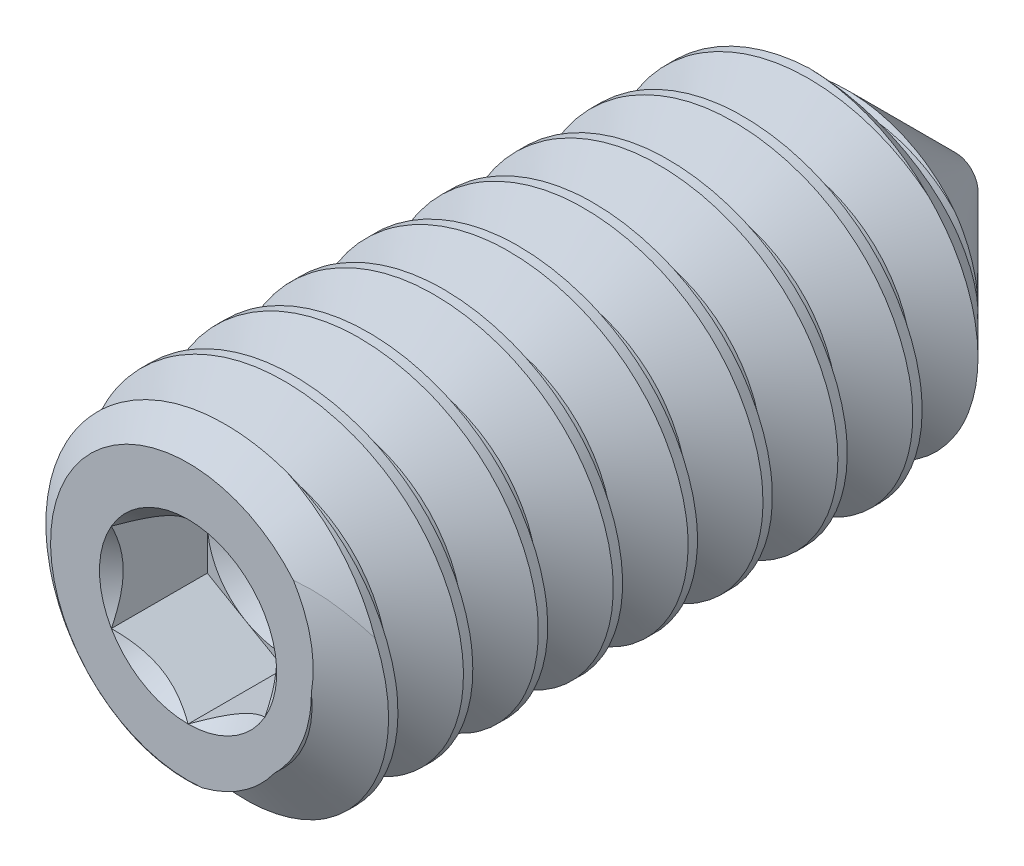
SolidWorks part; units mm, degrees
ref_plane "Front" through (0, 0, 0) normal (0, 0, 1) x (1, 0, 0)
ref_plane "Top" through (0, 0, 0) normal (0, 1, 0) x (1, 0, 0)
ref_plane "Right" through (0, 0, 0) normal (1, 0, 0) x (0, 0, -1)
sketch "Sketch22" plane through (0, 0, 0) normal (1, 0, 0) x (0, 0, -1)
  line L0 (-3.175, 0) -> (-3.175, 1.1379)
  line L1 (-3.175, 1.1379) -> (-2.9758, 1.4224)
  line L2 (-2.9758, 1.4224) -> (1.9375, 1.4224)
  line L3 (1.9375, 1.4224) -> (3.175, 0.1849)
  line L4 (-3.175, 1.1379) -> (-3.175, -1.1379) construction
  line L5 (3.175, 0) -> (-3.175, 0)
  line L6 (0, 1.4224) -> (0, -1.4224) construction
  line L8 (3.175, 0.1849) -> (3.175, 0)
  line L9 (-3.175, -1.4224) -> (3.175, -1.4224) construction
  line L10 (3.175, 0.1849) -> (3.175, -0.1849) construction
  line L11 (3.175, -0.1849) -> (1.9375, -1.4224) construction
  line L13 (3.175, 0.1849) -> (2.9901, 0) construction
  line L15 (2.9901, 0) -> (3.175, -0.1849) construction
  dimension "D1" = 90
  dimension "Dia" = 2.8448
  dimension "D2" = 0.3698
  dimension "Length" = 6.35
  dimension "D3" = 35
  dimension "D4" = 90
  dimension "D7" = 2.2758
revolve "Revolve1" add sketch "Sketch22" angle 360 about L5
ref_plane "Plane1" through (0, 0, -3.175) normal (0, 0, 1) x (1, 0, 0)
sketch "Sketch27" plane through (0, 0, -3.175) normal (0, 0, 1) x (1, 0, 0)
  circle A0 centre (0, 0) radius 1.4224 construction
  circle A1 centre (0, 0) radius 1.4224
curve "Helix/Spiral1" pitch 0.6195 height 6.9695 radius 1.4224 centre (0, 0, -3.175) axis (0, 0, 1) start towards (0, 1, 0)
sketch "Sketch28" plane through (0, 0, 0) normal (1, 0, 0) x (0, 0, -1)
  line L0 (3.175, 1.4224) -> (3.7171, 1.4224)
  line L1 (3.7171, 1.4224) -> (3.4848, 1.02)
  line L2 (3.4848, 1.02) -> (3.4073, 1.02)
  line L3 (3.4073, 1.02) -> (3.175, 1.4224)
  line L4 (3.2912, 1.2212) -> (3.6009, 1.2212) construction
  line L6 (-2.9758, 1.4224) -> (1.9375, 1.4224) construction
  line L7 (3.175, 1.6085) -> (3.175, -1.6085) construction
  dimension "D1" = 0.0774
  dimension "D2" = 0.3098
  dimension "D3" = 60
sweep "Cut-Sweep2" cut profiles "Sketch28" path "Helix/Spiral1"
sketch "Sketch23" plane through (0, 0, 3.175) normal (0, 0, 1) x (1, 0, 0)
  line L1 (0, 0.7332) -> (-0.635, 0.3666)
  line L2 (-0.635, 0.3666) -> (-0.635, -0.3666)
  line L3 (-0.635, -0.3666) -> (0, -0.7332)
  line L4 (0, -0.7332) -> (0.635, -0.3666)
  line L5 (0.635, -0.3666) -> (0.635, 0.3666)
  line L6 (0.635, 0.3666) -> (0, 0.7332)
  circle A0 centre (0, 0) radius 0.635 construction
  dimension "Hex" = 1.27
extrude "Cut-Extrude10" cut sketch "Sketch23" against normal blind 0.7937
sketch "Sketch24" plane through (0, 0, 3.175) normal (0, 0, 1) x (1, 0, 0)
  circle A0 centre (0, 0) radius 0.7332
extrude "Cut-Extrude11" cut sketch "Sketch24" against normal through all draft 45
sketch "Sketch26" plane through (0, 0, 2.3812) normal (0, 0, 1) x (1, 0, 0)
  circle A0 centre (0, 0) radius 0.635 construction
  circle A1 centre (0, 0) radius 0.635
extrude "Cut-Extrude12" cut sketch "Sketch26" against normal through all draft 60
sketch "Sketch30" plane through (0, 0, 0) normal (1, 0, 0) x (0, 0, -1)
  line L0 (-2.9758, 1.4224) -> (1.9375, 1.4224) construction
  line L1 (-3.175, 0) -> (-3.175, 1.1379) construction
  line L3 (-3.175, -1.4224) -> (3.175, -1.4224) construction
  point P0 (-3.175, 1.4224)
  point P1 (1.9375, 1.4224)
  point P2 (1.9375, -1.4224)
  point P11 (1.0082, -1.4224)
  dimension "D1" = 0.9293
equation "\"D7@Sketch22\"=\"Dia@Sketch22\"*.8"
equation "\"D1@Sketch28\" = \"D4@Helix/Spiral1\" * .125"
equation "\"D3@Helix/Spiral1\" = \"Length@Sketch22\" + \"D4@Helix/Spiral1\""
equation "\"D1@Sketch30\" = \"D4@Helix/Spiral1\" * 1.5"
equation "\"hex Depth@Cut-Extrude10\" = \"Hex@Sketch23\" * .625"
equation "\"D2@Sketch28\" = \"D4@Helix/Spiral1\" * .5"
equation "\"D2@Sketch22\" = \"Dia@Sketch22\" * .13"
equation "\"D4@Sketch22\" = \"D1@Sketch22\""
